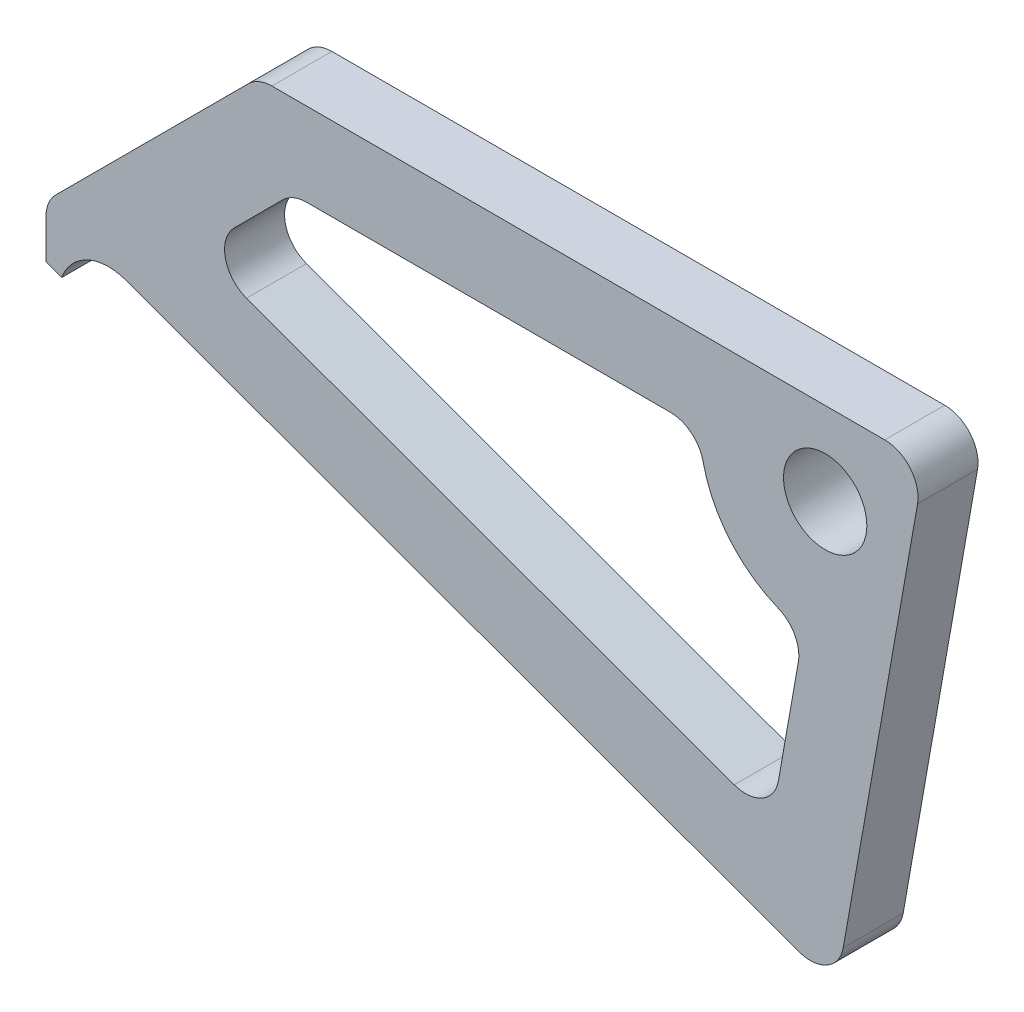
SolidWorks part; units mm, degrees
ref_plane "Front Plane" through (0, 0, 0) normal (0, 0, 1) x (1, 0, 0)
ref_plane "Top Plane" through (0, 0, 0) normal (0, 1, 0) x (1, 0, 0)
ref_plane "Right Plane" through (0, 0, 0) normal (1, 0, 0) x (0, 0, -1)
sketch "Sketch1" plane through (0, 0, 0) normal (0, 0, 1) x (-1, 0, 0)
  line L0 (263.6617, 63.6617) -> (200, 0)
  line L24 (263.6617, 63.6617) -> (26.449, 150)
  line L25 (26.449, 150) -> (0, 0)
  line L26 (0, 0) -> (200, 0)
  point P0 (0, 0)
  dimension "D1" = 80
  dimension "D2" = 150
  dimension "D3" = 20
  dimension "D4" = 200
  dimension "D5" = 45
sketch "Sketch3" plane through (0, 0, 0) normal (0, 0, 1) x (1, 0, 0)
  line L0 (300, 855) -> (1500, 855) construction
  line L1 (-324.126, -813.8422) -> (-1524.126, -813.8422) construction
sketch "Sketch4" plane through (0, 0, 0) normal (0, 0, 1) x (1, 0, 0)
  line L0 (-258.9632, -81.3344) -> (-263.6617, -79.6243)
  line L1 (-263.6617, -67.8038) -> (-263.6617, -79.6243)
  line L2 (-192.5736, -27.9289) -> (-207.1363, -42.4916)
  line L4 (-200, 0) -> (-263.6617, -63.6617)
  line L5 (-263.6617, -63.6617) -> (-26.449, -150)
  line L6 (-26.449, -150) -> (0, 0)
  line L7 (0, 0) -> (-200, 0)
  line L8 (-202.9289, -2.9289) -> (-260.7327, -60.7327)
  line L9 (-239.7375, -72.3693) -> (-37.6479, -145.924)
  line L10 (-24.3796, -138.2635) -> (-2.0695, -11.7365)
  line L11 (-11.9175, 0) -> (-195.8579, 0)
  line L13 (-203.4854, -58.9596) -> (-57.0944, -112.2416)
  line L14 (-43.8261, -104.5811) -> (-37.8573, -70.73)
  line L16 (-76.2293, -25) -> (-185.5025, -25)
  line L17 (-218.2356, -53.591) -> (-45.8956, -116.3176) construction
  line L18 (-29.7938, -25) -> (-189.6447, -25) construction
  line L19 (-45.8956, -116.3176) -> (-29.7938, -25) construction
  line L20 (-189.6447, -25) -> (-218.2356, -53.591) construction
  line L21 (-218.2356, -53.591) -> (-218.2356, -53.591) construction
  line L22 (-218.2356, -53.591) -> (-218.2356, -53.591) construction
  arc A1 (-239.7375, -72.3693) -> (-258.9632, -81.3344) centre (-244.8678, -86.4647) ccw
  circle A2 centre (-29.7938, -25) radius 12.5
  arc A3 (-260.7327, -60.7327) -> (-263.6617, -67.8038) centre (-253.6617, -67.8038) ccw
  arc A4 (-202.9289, -2.9289) -> (-195.8579, 0) centre (-195.8579, -10) cw
  arc A5 (-2.0695, -11.7365) -> (-11.9175, 0) centre (-11.9175, -10) ccw
  arc A6 (-37.6479, -145.924) -> (-24.3796, -138.2635) centre (-34.2277, -136.527) ccw
  arc A10 (-29.7938, -25) -> (-29.7938, -25) centre (-29.7938, -25) ccw
  arc A12 (-66.4534, -32.8947) -> (-43.9345, -59.7317) centre (-29.7938, -25) ccw
  arc A13 (-66.4534, -32.8947) -> (-76.2293, -25) centre (-76.2293, -35) ccw
  circle A14 centre (-29.7938, -25) radius 37.5 construction
  arc A15 (-43.9345, -59.7317) -> (-37.8573, -70.73) centre (-47.7053, -68.9935) cw
  arc A16 (-43.8261, -104.5811) -> (-57.0944, -112.2416) centre (-53.6742, -102.8446) cw
  arc A17 (-45.8956, -116.3176) -> (-45.8956, -116.3176) centre (-45.8956, -116.3176) ccw construction
  arc A18 (-185.5025, -25) -> (-192.5736, -27.9289) centre (-185.5025, -35) ccw
  arc A19 (-189.6447, -25) -> (-189.6447, -25) centre (-189.6447, -25) cw construction
  arc A20 (-203.4854, -58.9596) -> (-207.1363, -42.4916) centre (-200.0652, -49.5627) cw
  arc A21 (-218.2356, -53.591) -> (-218.2356, -53.591) centre (-218.2356, -53.591) cw construction
  arc A22 (-218.2356, -53.591) -> (-218.2356, -53.591) centre (-218.2356, -53.591) ccw construction
  point P40 (7.7062, -25)
  dimension "D2" = 30
  dimension "D5" = 25
  dimension "D8" = 10
  dimension "D11" = 10
  dimension "D12" = 10
  dimension "D3" = 15
  dimension "D4" = 5
  dimension "D6" = 25
  dimension "D7" = 25
  dimension "D1" = 0
  dimension "D9" = 25
  dimension "D10" = 25
extrude "Boss-Extrude1" add sketch "Sketch4" along normal blind 18 contours L9 A6 L10 A5 L11 A4 L8 A3 L1 L0 A1 A2 L13 A20 L2 A18 L16 A13 A12 A15 L14 A16 region at (-257.473, -71.9671, 0) region at (-250.2884, -65.3441, 0)
